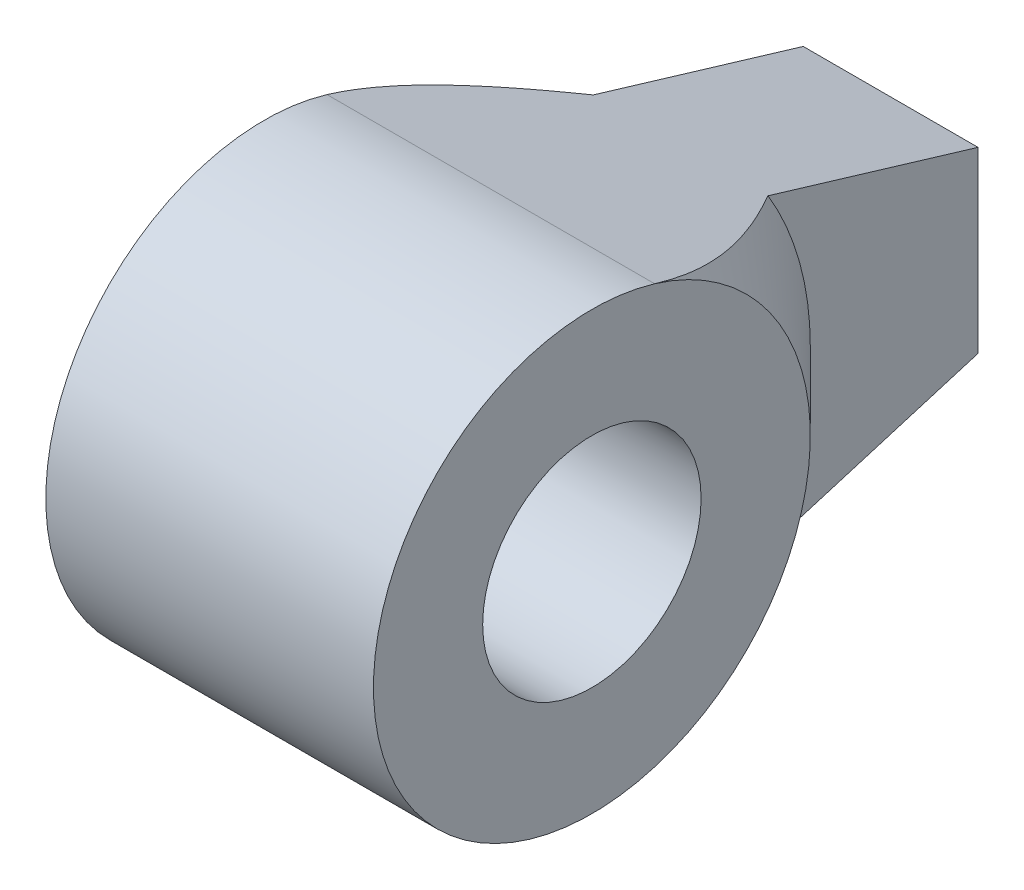
SolidWorks part; units mm, degrees
material "201 Annealed Stainless Steel (SS)"
ref_plane "Front Plane" through (0, 0, 0) normal (0, 0, 1) x (1, 0, 0)
ref_plane "Top Plane" through (0, 0, 0) normal (0, 1, 0) x (1, 0, 0)
ref_plane "Right Plane" through (0, 0, 0) normal (1, 0, 0) x (0, 0, -1)
sketch "Sketch11" plane through (0, 0, 0) normal (1, 0, 0) x (0, 0, -1)
  line L5 (42.352, -8.1723) -> (42.352, 8.1723)
  line L9 (42.352, 5.1723) -> (20, 5.1723) construction
  line L10 (20, 5.1723) -> (20, -5.1723) construction
  line L11 (20, -5.1723) -> (42.352, -5.1723) construction
  line L12 (0, 0) -> (92.3794, 0) construction
  line L13 (0, 20) -> (0, 0) construction
  line L14 (5.7483, 19.1561) -> (42.352, 8.1723)
  line L15 (42.352, -8.1723) -> (5.7483, -19.1561)
  circle A0 centre (0, 0) radius 10
  arc A1 (5.7483, 19.1561) -> (5.7483, -19.1561) centre (0, 0) ccw
  arc A2 (0, -20) -> (0, 20) centre (0, 0) ccw construction
  point P0 (0, 0)
  point P4 (32.7535, 19.8688)
  point P10 (0, 0)
  dimension "D3" = 20
  dimension "D4" = 10.3446
  dimension "D2" = 10
  dimension "D1" = 22.352
  dimension "D5" = 3
extrude "Boss-Extrude3" add sketch "Sketch11" along normal mid plane 16 contours A0 | A1 L15 L5 L14 region at (0, 0, 0)
sketch "Sketch14" plane through (0, 0, 0) normal (1, 0, 0) x (0, 0, -1)
  circle A1 centre (0, 0) radius 20
  circle A2 centre (0, 0) radius 10
  arc A3 (5.7483, 19.1561) -> (5.7483, -19.1561) centre (0, 0) ccw construction
  circle A4 centre (0, 0) radius 10 construction
extrude "Boss-Extrude4" add sketch "Sketch14" along normal mid plane 30
chamfer "Chamfer2" distance 7 angle 45 2 edges at (-8, 0, -20) (8, 0, -20)
sketch "Sketch16" plane through (0, 0, -42.352) normal (0, 0, -1) x (-1, 0, 0)
  point P0 (0, 0)
hole_wizard "1/2-20 Tapped Hole2" positions "3DSketch7" profile "Sketch17" tap size "1/2-20" standard "ANSI Inch"
sketch3d "3DSketch7"
  point P0 (0, 0, -42.352)
sketch "Sketch17" plane through (0, 0, -42.352) normal (1, 0, 0) x (0, 1, 0)
  line L0 (0, 0) -> (0, 25.8096)
  line L1 (0, 25.8096) -> (5.7544, 22.352)
  line L2 (5.7544, 22.352) -> (5.7544, 0)
  line L5 (5.7544, 0) -> (0, 0)
  line L10 (0, 25.8096) -> (-5.7544, 22.352) construction
  line L11 (0, -6.35) -> (0, 107.95) construction
  dimension "Tap Drill Dia." = 11.5087
  dimension "Tap Drill Depth" = 22.352
  dimension "Drill Angle" = 118
